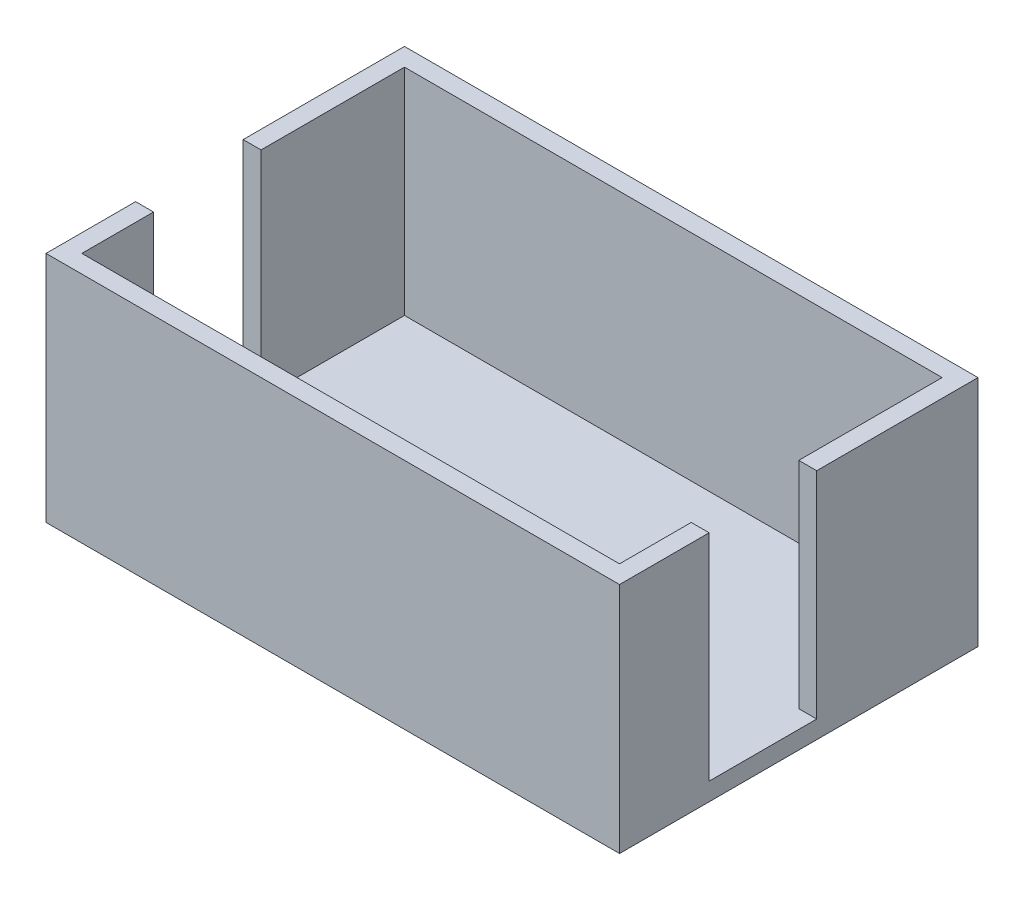
SolidWorks part; units mm, degrees
ref_plane "Front Plane" through (0, 0, 0) normal (0, 0, 1) x (1, 0, 0)
ref_plane "Top Plane" through (0, 0, 0) normal (0, 1, 0) x (1, 0, 0)
ref_plane "Right Plane" through (0, 0, 0) normal (1, 0, 0) x (0, 0, -1)
sketch "Sketch1" plane through (0, 0, 0) normal (0, 1, 0) x (1, 0, 0)
  line L1 (0, 0) -> (160, 0)
  line L2 (0, 0) -> (0, 100)
  line L3 (0, 100) -> (160, 100)
  line L4 (160, 0) -> (160, 100)
  dimension "D1" = 100
  dimension "D2" = 160
extrude "Boss-Extrude1" add sketch "Sketch1" along normal blind 5
sketch "Sketch3" plane through (0, 5, 0) normal (0, 1, 0) x (1, 0, 0)
  line L11 (5, 5) -> (5, 25)
  line L12 (5, 25) -> (0, 25)
  line L13 (0, 100) -> (0, 0) construction
  line L14 (80, 0) -> (80, 100) construction
  line L15 (155, 5) -> (155, 95)
  line L16 (5, 5) -> (155, 5)
  line L17 (5, 95) -> (5, 5)
  line L18 (155, 95) -> (5, 95)
  line L19 (155, 5) -> (155, 95)
  line L20 (5, 5) -> (155, 5)
  line L21 (5, 95) -> (5, 5)
  line L22 (155, 95) -> (5, 95)
  line L23 (0, 0) -> (160, 0) construction
  line L24 (160, 100) -> (0, 100) construction
  line L25 (155, 25) -> (160, 25)
  line L26 (5, 95) -> (5, 55)
  line L27 (5, 55) -> (0, 55)
  line L28 (155, 55) -> (160, 55)
  line M5 (0, 100) -> (0, 0)
  line M6 (0, 0) -> (160, 0)
  line M7 (160, 0) -> (160, 100)
  line M8 (160, 100) -> (0, 100)
  dimension "D2" = 20
  dimension "D3" = 40
  dimension "D1" = 5
extrude "Boss-Extrude2" add sketch "Sketch3" along normal blind 60 contours L14 L20 L11 L12 M6 M5 | L14 L25 L19 L20 M6 M7 | L14 L22 L19 L28 M7 M8 | L22 L14 L27 L21 M8 M5 region at (42.5, 5, -4.1618) region at (117.5, 5, -4.1618) region at (2.5, 5, -55.9179) region at (80.9179, 5, -97.5)
